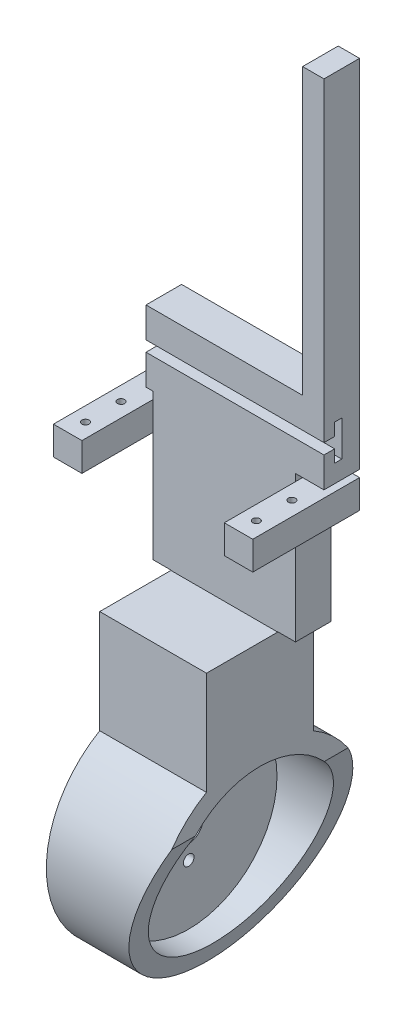
SolidWorks part; units mm, degrees
ref_plane "Front Plane" through (0, 0, 0) normal (0, 0, 1) x (1, 0, 0)
ref_plane "Top Plane" through (0, 0, 0) normal (0, 1, 0) x (1, 0, 0)
ref_plane "Right Plane" through (0, 0, 0) normal (1, 0, 0) x (0, 0, -1)
sketch "Sketch2" plane through (0, 0, 0) normal (1, 0, 0) x (0, 0, -1)
  line L1 (-15, 35) -> (15, 35)
  line L2 (-15, 35) -> (-15, -35)
  line L4 (15, 35) -> (15, -35)
  line L5 (-15, 35) -> (15, -35) construction
  line L6 (-15, -35) -> (15, 35) construction
  arc A0 (-15, -35) -> (15, -35) centre (0, -60.9808) ccw
  point P0 (0, 0)
  dimension "D1" = 70
  dimension "D2" = 30
extrude "Boss-Extrude1" add sketch "Sketch2" along normal blind 30
ref_plane "Plane1" through (30, 0, 0) normal (1, 0, 0) x (0, 0, -1)
sketch "Sketch6" plane through (0, 0, 0) normal (0, 0, 1) x (1, 0, 0)
  line L0 (15, 35) -> (30, -15.1451)
  line L1 (30, 35) -> (0, 35) construction
  line L2 (30, -27.2323) -> (30, 27.2323) construction
  line L3 (30, -15.1451) -> (30, -44.0365)
  line L4 (30, -44.0365) -> (15, -91.5431)
  line L5 (15, -91.5431) -> (48.5663, -91.5431)
  line L6 (48.5663, -91.5431) -> (48.5663, 35)
  line L7 (48.5663, 35) -> (15, 35)
extrude "Cut-Extrude4" cut sketch "Sketch6" against normal blind 40 and the other way blind 40
sketch "Sketch7" plane through (0, 0, 0) normal (0, 0, 1) x (1, 0, 0)
  line L2 (0, 35) -> (30, 35)
  line L3 (0, 35) -> (0, -31.934)
  line L4 (0, -31.934) -> (30, -31.934)
  line L5 (30, 35) -> (30, -31.934)
  dimension "D1" = 30
extrude "Boss-Extrude2" add sketch "Sketch7" along normal blind 15 and the other way blind 15
ref_plane "Plane4" through (0, 0, 15) normal (0, 0, 1) x (1, 0, 0)
sketch "Sketch12" plane through (0, 0, 15) normal (0, 0, 1) x (1, 0, 0)
  line L0 (0, 35) -> (0, -35) construction
  line L1 (30, 35) -> (0, 35)
  line L2 (30, 35) -> (30, -6)
  line L3 (30, -6) -> (0, -6)
  line L4 (0, 35) -> (0, -6)
  dimension "D1" = 41
extrude "Cut-Extrude7" cut sketch "Sketch12" against normal blind 20
ref_plane "Plane5" through (0, 0, -5) normal (0, 0, 1) x (1, 0, 0)
sketch "Sketch13" plane through (0, 0, -5) normal (0, 0, 1) x (1, 0, 0)
  line L0 (30, -6) -> (30, 35) construction
  line L5 (35, 35.0963) -> (-5, 35.0963)
  line L6 (35, 35.0963) -> (35, -5.9037)
  line L7 (35, -5.9037) -> (-5, -5.9037)
  line L8 (-5, 35.0963) -> (-5, -5.9037)
  dimension "D1" = 40
  dimension "D2" = 41
  dimension "D3" = 5
extrude "Boss-Extrude4" add sketch "Sketch13" against normal blind 10
sketch "Sketch15" plane through (0, 0, -5) normal (0, 0, 1) x (1, 0, 0)
  line L0 (35, -5.9037) -> (35, 35.0963) construction
  line L1 (35, 33.0963) -> (43, 33.0963)
  line L2 (35, 33.0963) -> (35, 25.0963)
  line L3 (35, 25.0963) -> (43, 25.0963)
  line L4 (43, 33.0963) -> (43, 25.0963)
  line L5 (30, -5.9037) -> (35, -5.9037) construction
  line L6 (-5, 35.0963) -> (-5, -5.9037) construction
  line L7 (-5, 33.0963) -> (-13, 33.0963)
  line L8 (-5, 33.0963) -> (-5, 25.0963)
  line L9 (-5, 25.0963) -> (-13, 25.0963)
  line L10 (-13, 33.0963) -> (-13, 25.0963)
  dimension "D1" = 8
  dimension "D2" = 8
  dimension "D3" = 31
  dimension "D4" = 8
extrude "Boss-Extrude5" add sketch "Sketch15" along normal blind 20 and the other way blind 10
ref_plane "Plane7" through (0, 33.0963, 0) normal (0, 1, 0) x (1, 0, 0)
sketch "Sketch17" plane through (0, 33.0963, 0) normal (0, 1, 0) x (1, 0, 0)
  line L0 (35, 5) -> (35, -15) construction
  line L1 (43, -15) -> (35, -15) construction
  line L2 (-5, 5) -> (-5, -15) construction
  circle A0 centre (39, 0) radius 1
  circle A1 centre (39, -10) radius 1
  circle A2 centre (-9, 0) radius 1
  circle A3 centre (-9, -10) radius 1
  dimension "D1" = 2
  dimension "D2" = 2
  dimension "D3" = 10
  dimension "D4" = 4
  dimension "D5" = 5
  dimension "D6" = 2
  dimension "D7" = 2
  dimension "D8" = 4
  dimension "D9" = 4
  dimension "D10" = 10
extrude "Cut-Extrude9" cut sketch "Sketch17" against normal blind 30
sketch "Sketch18" plane through (30, 0, 0) normal (1, 0, 0) x (0, 0, -1)
  circle A0 centre (0, -60.9808) radius 24.8063
  arc A1 (-24.7567, -44.0365) -> (24.7567, -44.0365) centre (0, -60.9808) ccw construction
  dimension "D1" = 0
extrude "Cut-Extrude10" cut sketch "Sketch18" against normal blind 20
sketch "Sketch19" plane through (30, 0, 0) normal (1, 0, 0) x (0, 0, -1)
  circle A2 centre (0, -60.9808) radius 4
  circle A4 centre (0, -52.9808) radius 1.5
  circle A5 centre (0, -68.9808) radius 1.5
  dimension "D1" = 3
  dimension "D2" = 3
  dimension "D3" = 8
  dimension "8" = 8
  dimension "D4" = 8
extrude "Cut-Extrude11" cut sketch "Sketch19" against normal blind 30
sketch "Sketch20" plane through (0, 0, -5) normal (0, 0, 1) x (1, 0, 0)
  line L8 (43, 25.0963) -> (43, 33.0963) construction
  line L9 (-13, 135.0963) -> (43, 135.0963)
  line L10 (-13, 135.0963) -> (-13, 35.0963)
  line L11 (-13, 35.0963) -> (43, 35.0963)
  line L12 (43, 135.0963) -> (43, 35.0963)
  line L13 (-13, 33.0963) -> (-13, 25.0963) construction
  line L14 (35, 35.0963) -> (-5, 35.0963) construction
  dimension "D1" = 0
  dimension "D2" = 0
  dimension "D3" = 0
  dimension "D4" = 100
extrude "Boss-Extrude6" add sketch "Sketch20" against normal blind 10
sketch "Sketch24" plane through (0, 0, -5) normal (0, 0, 1) x (1, 0, 0)
  line L1 (-13, 135.0963) -> (37, 135.0963)
  line L2 (-13, 135.0963) -> (-13, 55.0963)
  line L3 (-13, 55.0963) -> (37, 55.0963)
  line L4 (37, 135.0963) -> (37, 55.0963)
  dimension "D1" = 80
  dimension "D2" = 50
extrude "Cut-Extrude13" cut sketch "Sketch24" against normal blind 20
ref_plane "Plane9" through (43, 0, 0) normal (1, 0, 0) x (0, 0, -1)
sketch "Sketch25" plane through (43, 0, 0) normal (1, 0, 0) x (0, 0, -1)
  line L1 (10, 50.0963) -> (8, 50.0963)
  line L2 (10, 50.0963) -> (10, 40.0963)
  line L3 (10, 40.0963) -> (8, 40.0963)
  line L5 (8, 46.5963) -> (3.3303, 46.5963)
  line L7 (8, 43.5963) -> (3.3303, 43.5963)
  line L8 (3.3303, 46.5963) -> (3.3303, 43.5963)
  line L9 (15, 55.0963) -> (5, 55.0963) construction
  line L10 (8, 50.0963) -> (8, 46.5963)
  line L11 (8, 43.5963) -> (8, 40.0963)
  line L12 (5, 35.0963) -> (5, 135.0963) construction
  dimension "D1" = 3
  dimension "D2" = 2
  dimension "D3" = 5
  dimension "D4" = 10
  dimension "D5" = 3.5
  dimension "D6" = 3
  dimension "D7" = 2
extrude "Cut-Extrude14" cut sketch "Sketch25" against normal blind 70
sketch "Sketch30" plane through (0, 0, -5) normal (0, 0, 1) x (1, 0, 0)
  line L0 (-13, 55.0963) -> (37, 55.0963) construction
  line L1 (-13, 35.0963) -> (-7, 35.0963)
  line L2 (-13, 35.0963) -> (-13, 55.0963)
  line L3 (-13, 55.0963) -> (-7, 55.0963)
  line L4 (-7, 35.0963) -> (-7, 55.0963)
  dimension "D1" = 6
extrude "Cut-Extrude15" cut sketch "Sketch30" against normal blind 30
